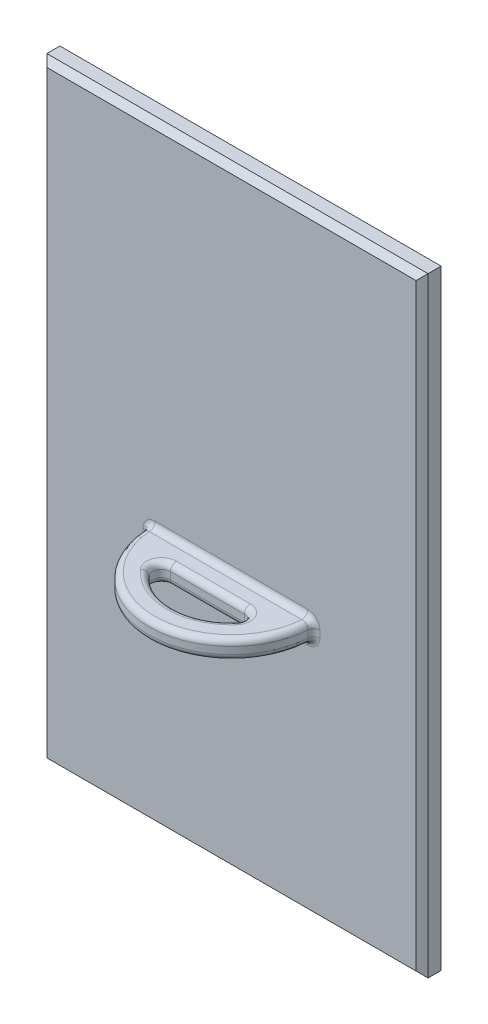
SolidWorks part; units mm, degrees
ref_plane "Front Plane" through (0, 0, 0) normal (0, 0, 1) x (1, 0, 0)
ref_plane "Top Plane" through (0, 0, 0) normal (0, 1, 0) x (1, 0, 0)
ref_plane "Right Plane" through (0, 0, 0) normal (1, 0, 0) x (0, 0, -1)
sketch "Sketch1" plane through (0, 0, 0) normal (0, 0, 1) x (1, 0, 0)
  line L1 (-31.75, 50.8) -> (31.75, 50.8)
  line L2 (-31.75, 50.8) -> (-31.75, -50.8)
  line L3 (-31.75, -50.8) -> (31.75, -50.8)
  line L4 (31.75, 50.8) -> (31.75, -50.8)
  line L5 (-31.75, 50.8) -> (31.75, -50.8) construction
  line L6 (-31.75, -50.8) -> (31.75, 50.8) construction
  point P0 (0, 0)
  dimension "D1" = 63.5
  dimension "D2" = 101.6
extrude "Boss-Extrude1" add sketch "Sketch1" along normal blind 3.175 contours L2 L3 L4 L1
sketch "Sketch2" plane through (0, 0, 0) normal (0, 0, -1) x (-1, 0, 0)
  line L1 (-23.33, -48.0907) -> (23.33, -48.0907) construction
  line L2 (-23.33, -48.0907) -> (-23.33, 26.3313) construction
  line L3 (-23.33, 26.3313) -> (23.33, 26.3313) construction
  line L4 (31.75, 50.8) -> (-31.75, 50.8)
  line L5 (-31.75, 50.8) -> (-31.75, -50.8)
  line L6 (-31.75, -50.8) -> (31.75, -50.8)
  line L7 (31.75, -50.8) -> (31.75, 50.8)
  line L8 (31.75, 50.8) -> (-31.75, 50.8)
  line L9 (-31.75, 50.8) -> (-31.75, -50.8)
  line L10 (-31.75, -50.8) -> (31.75, -50.8)
  line L11 (31.75, -50.8) -> (31.75, 50.8)
  line L12 (23.33, -48.0907) -> (23.33, 26.3313) construction
  line L13 (-23.33, -48.0907) -> (23.33, 26.3313) construction
  line L14 (-23.33, 26.3313) -> (23.33, -48.0907) construction
  line L22 (-22.2625, -45.0232) -> (-22.2625, 23.2638)
  line L23 (-20.2625, 25.2638) -> (20.2625, 25.2638)
  line L24 (22.2625, -45.0232) -> (22.2625, 23.2638)
  line L25 (-20.2625, -47.0232) -> (20.2625, -47.0232)
  line L26 (-19.0875, -41.8482) -> (-19.0875, 20.0888)
  line L27 (-17.0875, 22.0888) -> (17.0875, 22.0888)
  line L28 (19.0875, -41.8482) -> (19.0875, 20.0888)
  line L29 (-17.0875, -43.8482) -> (17.0875, -43.8482)
  line L30 (-23.85, -48.6107) -> (-23.85, 26.8513) construction
  line L31 (-23.85, 26.8513) -> (23.85, 26.8513) construction
  line L32 (23.85, -48.6107) -> (23.85, 26.8513) construction
  line L33 (-23.85, -48.6107) -> (23.85, -48.6107) construction
  line L34 (-19.0875, -43.8482) -> (-19.0875, 22.0888) construction
  line L35 (-19.0875, 22.0888) -> (19.0875, 22.0888) construction
  line L36 (-22.2625, -47.0232) -> (-22.2625, 25.2638) construction
  line L37 (-22.2625, -47.0232) -> (22.2625, -47.0232) construction
  line L38 (-19.0875, -43.8482) -> (19.0875, -43.8482) construction
  line L39 (22.2625, -47.0232) -> (22.2625, 25.2638) construction
  line L40 (19.0875, -43.8482) -> (19.0875, 22.0888) construction
  line L41 (-22.2625, 25.2638) -> (22.2625, 25.2638) construction
  arc A0 (-19.0875, 20.0888) -> (-17.0875, 22.0888) centre (-17.0875, 20.0888) cw
  arc A1 (-22.2625, -45.0232) -> (-20.2625, -47.0232) centre (-20.2625, -45.0232) ccw
  arc A2 (-17.0875, -43.8482) -> (-19.0875, -41.8482) centre (-17.0875, -41.8482) cw
  arc A3 (20.2625, -47.0232) -> (22.2625, -45.0232) centre (20.2625, -45.0232) ccw
  arc A4 (17.0875, -43.8482) -> (19.0875, -41.8482) centre (17.0875, -41.8482) ccw
  arc A5 (17.0875, 22.0888) -> (19.0875, 20.0888) centre (17.0875, 20.0888) cw
  arc A6 (22.2625, 23.2638) -> (20.2625, 25.2638) centre (20.2625, 23.2638) ccw
  arc A7 (-22.2625, 23.2638) -> (-20.2625, 25.2638) centre (-20.2625, 23.2638) cw
  point P2 (0, -10.8797)
  dimension "D7" = 2
  dimension "D8" = 2
  dimension "D2" = 46.66
  dimension "D3" = 74.422
  dimension "D4" = 1.0675
  dimension "D5" = 3.175
  dimension "D1" = 0
  dimension "D6" = 1.5875
extrude "Boss-Extrude2" add sketch "Sketch2" along normal blind 8.7312 contours A7 L22 A1 L25 A3 L24 A6 L23 L27 A5 L28 A4 L29 A2 L26 A0 region at (21.4135, -10.8797, 0)
sketch "Sketch3" plane through (0, 0, 3.175) normal (0, 0, 1) x (1, 0, 0)
  line L0 (0, 50.8) -> (0, -56.8463) construction
  line L1 (-13.75, -7.6332) -> (13.75, -7.6332)
  line L2 (-13.75, -7.6332) -> (-13.75, -10.8082)
  line L3 (-13.75, -10.8082) -> (13.75, -10.8082)
  line L4 (31.75, 50.8) -> (-31.75, 50.8)
  line L5 (-31.75, 50.8) -> (-31.75, -50.8)
  line L6 (-31.75, -50.8) -> (31.75, -50.8)
  line L7 (31.75, -50.8) -> (31.75, 50.8)
  line L8 (31.75, 50.8) -> (-31.75, 50.8)
  line L9 (-31.75, 50.8) -> (-31.75, -50.8)
  line L10 (-31.75, -50.8) -> (31.75, -50.8)
  line L11 (31.75, -50.8) -> (31.75, 50.8)
  line L12 (13.75, -7.6332) -> (13.75, -10.8082)
  line L13 (-13.75, -7.6332) -> (13.75, -10.8082) construction
  line L14 (-13.75, -10.8082) -> (13.75, -7.6332) construction
  point P2 (0, -9.2207)
  point P4 (0, -9.2207)
  point P10 (0, 3.7777)
  point P11 (0, -9.2207)
  dimension "D2" = 3.175
  dimension "D3" = 27.5
  dimension "D1" = 0
extrude "Boss-Extrude3" add sketch "Sketch3" along normal blind 27.5 contours L2 L1 L12 L3
sketch "Sketch4" plane through (0, -10.8082, 0) normal (0, -1, 0) x (1, 0, 0)
  line L0 (-13.75, 3.175) -> (13.75, 3.175) construction
  line L1 (-13.75, 3.175) -> (13.75, 3.175)
  arc A0 (-13.75, 3.175) -> (13.75, 3.175) centre (0, 3.175) cw
  line M2 (13.75, 3.175) -> (13.75, 30.675)
  line M3 (13.75, 30.675) -> (-13.75, 30.675)
  line M4 (-13.75, 30.675) -> (-13.75, 3.175)
extrude "Cut-Extrude1" cut sketch "Sketch4" against normal blind 27.5 contours A0 M4 M2 M3 region at (0, -10.8082, 22.0426)
sketch "Sketch5" plane through (0, -7.6332, 0) normal (0, 1, 0) x (1, 0, 0)
  line L0 (6.1492, -7.175) -> (-6.1492, -7.175)
  line L1 (13.75, -3.175) -> (-13.75, -3.175)
  line L2 (13.75, -3.175) -> (-13.75, -3.175)
  line L3 (8.8917, -7.175) -> (-8.8917, -7.175) construction
  arc A0 (-7.2672, -9.675) -> (7.2672, -9.675) centre (0, -3.175) ccw
  arc A1 (-13.75, -3.175) -> (13.75, -3.175) centre (0, -3.175) ccw
  arc A2 (-13.75, -3.175) -> (13.75, -3.175) centre (0, -3.175) ccw
  arc A3 (-8.8917, -7.175) -> (8.8917, -7.175) centre (0, -3.175) ccw construction
  arc A4 (7.2672, -9.675) -> (6.1492, -7.175) centre (6.1492, -8.675) ccw
  arc A5 (-7.2672, -9.675) -> (-6.1492, -7.175) centre (-6.1492, -8.675) cw
  dimension "D3" = 1.5
  dimension "D1" = 0
  dimension "D2" = 4
extrude "Cut-Extrude3" cut sketch "Sketch5" against normal blind 27.5 contours A0 A4 L0 A5
fillet "Fillet1" radius 1 6 edges at (0, -10.8082, 3.175) (0, -7.6332, 3.175) (13.75, -9.2207, 3.175) (0, -10.8082, 16.925) (-13.75, -9.2207, 3.175) (0, -7.6332, 16.925)
fillet "Fillet2" radius 1 8 edges at (7.5185, -10.8082, 8.0626) (7.5185, -7.6332, 8.0626) (0, -10.8082, 7.175) (0, -7.6332, 7.175) (-7.5185, -7.6332, 8.0626) (-7.5185, -10.8082, 8.0626) (0, -10.8082, 12.925) (0, -7.6332, 12.925)
chamfer "Chamfer1" distance 1 angle 45 4 edges at (0, -50.8, 3.175) (-31.75, 0, 3.175) (0, 50.8, 3.175) (31.75, 0, 3.175)
